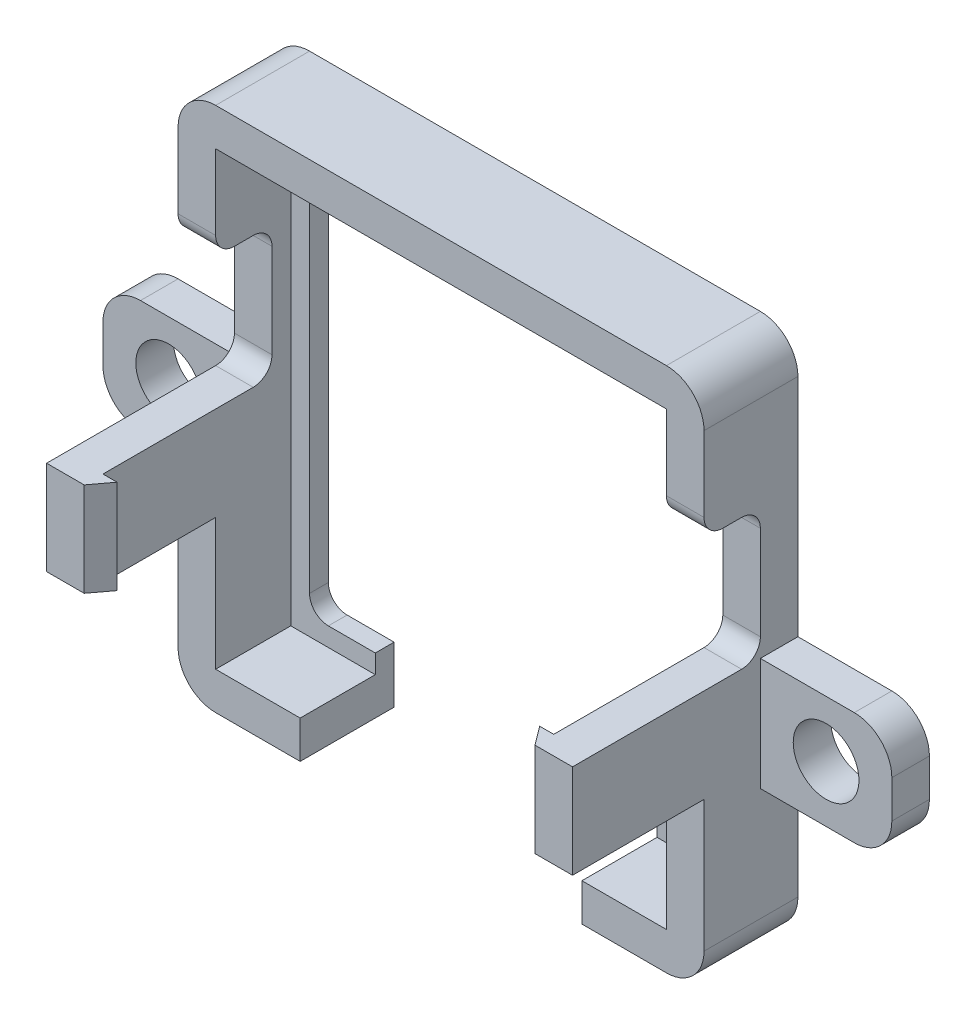
SolidWorks part; units mm, degrees
ref_plane "正面" through (0, 0, 0) normal (0, 0, 1) x (1, 0, 0)
ref_plane "平面" through (0, 0, 0) normal (0, 1, 0) x (1, 0, 0)
ref_plane "右側面" through (0, 0, 0) normal (1, 0, 0) x (0, 0, -1)
sketch "ｽｹｯﾁ1" plane through (0, 0, 0) normal (0, 0, 1) x (1, 0, 0)
  line L0 (-14, 14) -> (14, 14)
  line L1 (-12, 12) -> (12, 12)
  line L2 (-12, 12) -> (-12, -12)
  line L3 (-12, -12) -> (12, -12)
  line L4 (12, 12) -> (12, -12)
  line L5 (-12, 12) -> (12, -12) construction
  line L6 (-12, -12) -> (12, 12) construction
  line L7 (14, 14) -> (14, -14)
  line L8 (-14, -14) -> (14, -14)
  line L9 (-14, 14) -> (-14, -14)
  point P0 (0, 0)
  dimension "D1" = 24
  dimension "D2" = 2
  dimension "24.5" = 24
extrude "ﾎﾞｽ - 押し出し1" add sketch "ｽｹｯﾁ1" along normal blind 4 contours L0 L9 L8 L7 L1 L4 L3 L2 region at (0, 13.604, 0)
sketch "ｽｹｯﾁ2" plane through (0, -14, 0) normal (0, -1, 0) x (-1, 0, 0)
  line L0 (0, 0) -> (0, -4) construction
  line L1 (14, -4) -> (-14, -4) construction
  line L3 (7.5, 0) -> (-7.5, 0)
  line L4 (7.5, 0) -> (7.5, -4)
  line L5 (7.5, -4) -> (-7.5, -4)
  line L6 (-7.5, 0) -> (-7.5, -4)
  line L7 (7.5, 0) -> (-7.5, -4) construction
  line L8 (7.5, -4) -> (-7.5, 0) construction
  point P5 (0, -2)
  dimension "D1" = 15
extrude "ｶｯﾄ - 押し出し1" cut sketch "ｽｹｯﾁ2" against normal up to next
sketch "ｽｹｯﾁ3" plane through (0, 0, 0) normal (0, 0, -1) x (-1, 0, 0)
  line L0 (-7.5, -11) -> (-10, -11)
  line L1 (-11, -10) -> (-11, 10)
  line L2 (-10, 11) -> (10, 11)
  line L3 (11, 10) -> (11, -10)
  line L4 (10, -11) -> (7.5, -11)
  line L5 (-7.5, -12) -> (-7.5, -11)
  line L6 (7.5, -12) -> (7.5, -11)
  line L12 (12, -12) -> (7.5, -12)
  line L13 (7.5, -12) -> (7.5, -14)
  line L14 (7.5, -14) -> (14, -14)
  line L15 (14, -14) -> (14, 14)
  line L16 (14, 14) -> (-14, 14)
  line L17 (-14, 14) -> (-14, -14)
  line L18 (-14, -14) -> (-7.5, -14)
  line L19 (-7.5, -14) -> (-7.5, -12)
  line L20 (-7.5, -12) -> (-12, -12)
  line L21 (-12, -12) -> (-12, 12)
  line L22 (-12, 12) -> (12, 12)
  line L23 (12, 12) -> (12, -12)
  line L24 (10, -12) -> (7.5, -12)
  line L25 (7.5, -12) -> (7.5, -14)
  line L26 (7.5, -14) -> (14, -14)
  line L27 (14, -14) -> (14, 14)
  line L28 (14, 14) -> (-14, 14)
  line L29 (-14, 14) -> (-14, -14)
  line L30 (-14, -14) -> (-7.5, -14)
  line L31 (-7.5, -14) -> (-7.5, -12)
  line L32 (-7.5, -12) -> (-10, -12)
  line L33 (-12, -10) -> (-12, 10)
  line L34 (-10, 12) -> (10, 12)
  line L35 (12, 10) -> (12, -10)
  arc A0 (10, 12) -> (12, 10) centre (10, 10) cw
  arc A1 (-12, 10) -> (-10, 12) centre (-10, 10) cw
  arc A2 (-10, -12) -> (-12, -10) centre (-10, -10) cw
  arc A3 (10, -12) -> (12, -10) centre (10, -10) ccw
  arc A4 (-10, -11) -> (-11, -10) centre (-10, -10) cw
  arc A5 (-11, 10) -> (-10, 11) centre (-10, 10) cw
  arc A6 (10, 11) -> (11, 10) centre (10, 10) cw
  arc A7 (10, -11) -> (11, -10) centre (10, -10) ccw
  line M17 (12, -12) -> (7.5, -12)
  line M18 (7.5, -12) -> (7.5, -14)
  line M19 (7.5, -14) -> (14, -14)
  line M20 (14, -14) -> (14, 14)
  line M21 (14, 14) -> (-14, 14)
  line M22 (-14, 14) -> (-14, -14)
  line M23 (-14, -14) -> (-7.5, -14)
  line M24 (-7.5, -14) -> (-7.5, -12)
  line M25 (-7.5, -12) -> (-12, -12)
  line M26 (-12, -12) -> (-12, 12)
  line M27 (-12, 12) -> (12, 12)
  line M28 (12, 12) -> (12, -12)
  dimension "D2" = 2
  dimension "D1" = 0
  dimension "D3" = 1
extrude "ﾎﾞｽ - 押し出し2" add sketch "ｽｹｯﾁ3" along normal blind 1 contours M28 M17 M18 M19 M20 M21 M22 M23 M24 M25 M26 M27 | A3 M17 M28 | A7 L4 L6 A3 A0 A1 A2 L5 L0 A4 L1 A5 L2 A6 L3 M17 M28 M27 M26 M25 | A2 M25 M26 | A1 M26 M27 | A0 M27 M28 region at (7.8394, -11.5, 0) region at (7.896, -13, 0) region at (11.5533, -11.5533, 0) region at (11.5533, 11.5533, 0) region at (-11.5533, 11.5533, 0) region at (-11.5533, -11.5533, 0)
sketch "ｽｹｯﾁ4" plane through (0, 0, 4) normal (0, 0, 1) x (1, 0, 0)
  line L0 (12, -2.61) -> (-12, -2.61) construction
  line L3 (12, 12) -> (12, -12) construction
  line L5 (-12, 12) -> (-12, -12) construction
  line L6 (14, 14) -> (14, -14) construction
  line L7 (14, 0) -> (12, 0)
  line L12 (14, 0) -> (14, -5)
  line L13 (14, -5) -> (12, -5)
  line L18 (12, 0) -> (12, -5)
  line L19 (0, -2.75) -> (0, 2.75) construction
  line L20 (-14, -5) -> (-12, -5)
  line L21 (-12, 0) -> (-12, -5)
  line L22 (-14, 0) -> (-12, 0)
  line L23 (-14, 0) -> (-14, -5)
  dimension "D1" = 2.61
  dimension "D2" = 2.61
  dimension "D3" = 2.39
extrude "ﾎﾞｽ - 押し出し3" add sketch "ｽｹｯﾁ4" along normal blind 7
sketch "ｽｹｯﾁ5" plane through (0, 0, 0) normal (0, 1, 0) x (1, 0, 0)
  line L0 (12, -11) -> (11.25, -10)
  line L1 (11.25, -10) -> (12, -10)
  line L3 (12, -11) -> (12, -10)
  line L4 (0, -6.6) -> (0, 6.6) construction
  line L5 (-12, -11) -> (-11.25, -10)
  line L6 (-12, -11) -> (-12, -10)
  line L7 (-11.25, -10) -> (-12, -10)
  line L8 (12, -11) -> (12, -4) construction
  point P11 (12, -10)
  dimension "D1" = 1
  dimension "0.5" = 0.75
extrude "ﾎﾞｽ - 押し出し7" add sketch "ｽｹｯﾁ5" against normal up to surface (5 mm away) up to face at (13, -5, 7.5)
sketch "ｽｹｯﾁ6" plane through (0, 0, -1) normal (0, 0, -1) x (-1, 0, 0)
  line L0 (14.25, -3.0876) -> (-14.25, -3.0876) construction
  line L3 (0, 11) -> (0, -11.1752) construction
  line L4 (21, -6) -> (14, -6)
  line L5 (-21, 0) -> (-14, 0)
  line L6 (-21, 0) -> (-21, -6)
  line L7 (-21, -6) -> (-14, -6)
  line L8 (-14, 0) -> (-14, -6)
  line L9 (-21, 0) -> (-14, -6) construction
  line L10 (-21, -6) -> (-14, 0) construction
  line L11 (14, 0) -> (14, -6)
  line L12 (21, 0) -> (14, 0)
  line L13 (21, 0) -> (21, -6)
  line L15 (-10, 11) -> (10, 11) construction
  line L16 (-14, 14) -> (-14, -14) construction
  line L17 (14, -14) -> (14, 14) construction
  circle A0 centre (17.5, -3) radius 1.75
  circle A1 centre (-17.5, -3) radius 1.75
  point P2 (0, -0.0876)
  dimension "D1" = 3.5
  dimension "D2" = 35
  dimension "D3" = 6
  dimension "D4" = 3
extrude "ﾎﾞｽ - 押し出し6" add sketch "ｽｹｯﾁ6" against normal blind 2
fillet "ﾌｨﾚｯﾄ1" radius 2 8 edges at (-14, 14, 1.5) (-14, -14, 1.5) (14, -14, 1.5) (14, 14, 1.5) (21, 0, 0) (21, -6, 0) (-21, 0, 0) (-21, -6, 0)
sketch "ｽｹｯﾁ8" plane through (-14, 0, 0) normal (-1, 0, 0) x (0, 0, 1)
  line L0 (4, 12) -> (4, 0) construction
  line L1 (4, 7) -> (1, 7)
  line L2 (4, 7) -> (4, 0)
  line L3 (4, 0) -> (1, 0)
  line L4 (1, 7) -> (1, 0)
  line L5 (4, 12) -> (-1, 12) construction
  point P8 (4, 0)
  dimension "D1" = 3
  dimension "D2" = 5
extrude "ｶｯﾄ - 押し出し3" cut sketch "ｽｹｯﾁ8" against normal through all
fillet "ﾌｨﾚｯﾄ2" radius 1 6 edges at (-13, 0, 1) (-13, 7, 1) (-13, 7, 4) (13, 0, 1) (13, 7, 1) (13, 7, 4)
